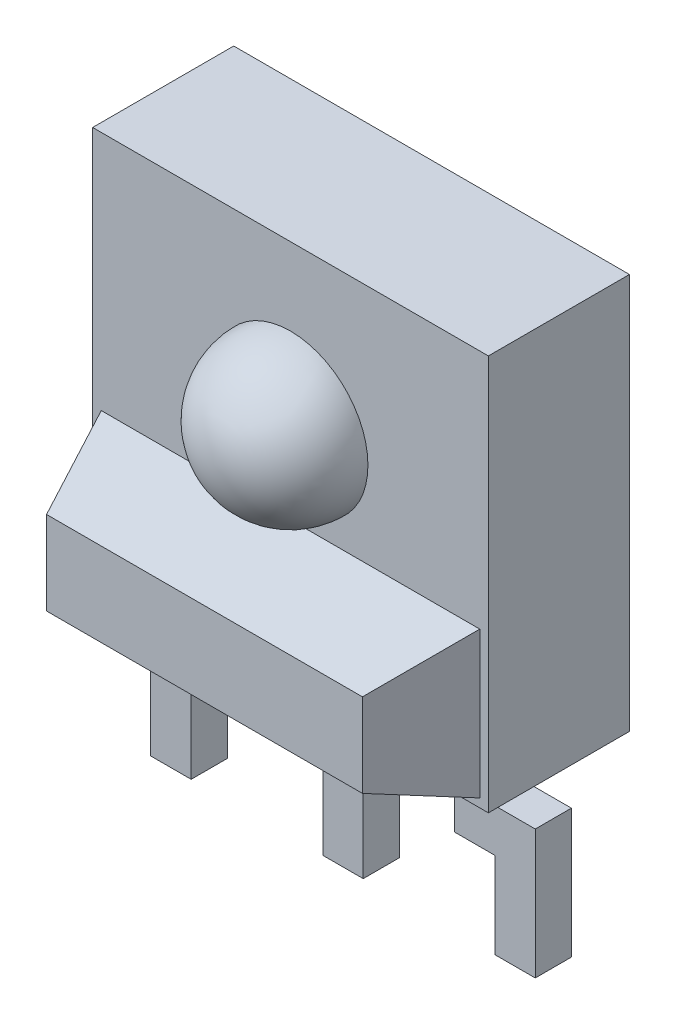
SolidWorks part; units mm, degrees
ref_plane "Front Plane" through (0, 0, 0) normal (0, 0, 1) x (1, 0, 0)
ref_plane "Top Plane" through (0, 0, 0) normal (0, 1, 0) x (1, 0, 0)
ref_plane "Right Plane" through (0, 0, 0) normal (1, 0, 0) x (0, 0, -1)
sketch "Sketch1" plane through (0, 0, 0) normal (0, 0, 1) x (1, 0, 0)
  line L0 (-1.295, 1) -> (-1.295, 0)
  line L1 (-0.235, 1) -> (0.235, 1)
  line L2 (-0.235, 1) -> (-0.235, -1)
  line L3 (-0.235, -1) -> (0.235, -1)
  line L4 (0.235, 1) -> (0.235, -1)
  line L5 (-0.235, 1) -> (0.235, -1) construction
  line L6 (-0.235, -1) -> (0.235, 1) construction
  line L7 (-1.295, 0) -> (-1.765, 0)
  line L8 (-1.765, 0) -> (-1.765, -1)
  line L9 (-1.765, -1) -> (-2.235, -1)
  line L10 (-2.235, -1) -> (-2.235, 0.5)
  line L11 (-2.235, 0.5) -> (-1.765, 0.5)
  line L12 (-1.765, 0.5) -> (-1.765, 1)
  line L13 (-1.765, 1) -> (-1.295, 1)
  line L14 (0, 1.2878) -> (0, -2.2675) construction
  line L15 (1.765, 1) -> (1.295, 1)
  line L16 (1.765, 0.5) -> (1.765, 1)
  line L17 (2.235, 0.5) -> (1.765, 0.5)
  line L18 (2.235, -1) -> (2.235, 0.5)
  line L19 (1.765, -1) -> (2.235, -1)
  line L20 (1.765, 0) -> (1.765, -1)
  line L21 (1.295, 0) -> (1.765, 0)
  line L22 (1.295, 1) -> (1.295, 0)
  point P0 (0, 0)
  point P13 (-2, -1)
  dimension "D1" = 0.47
  dimension "D2" = 2
  dimension "D3" = 0.47
  dimension "D4" = 0.47
  dimension "D5" = 1
  dimension "D6" = 1
  dimension "D7" = 0.5
  dimension "D8" = 2
  dimension "D9" = 0.47
extrude "Boss-Extrude1" add sketch "Sketch1" along normal mid plane 0.42
sketch "Sketch2" plane through (0, 1, 0) normal (0, 1, 0) x (1, 0, 0)
  line L1 (-2.3, 0.82) -> (2.3, 0.82)
  line L2 (-2.3, 0.82) -> (-2.3, -0.82)
  line L3 (-2.3, -0.82) -> (2.3, -0.82)
  line L4 (2.3, 0.82) -> (2.3, -0.82)
  line L5 (-2.3, 0.82) -> (2.3, -0.82) construction
  line L6 (-2.3, -0.82) -> (2.3, 0.82) construction
  point P0 (0, 0)
  dimension "D1" = 1.64
  dimension "D2" = 4.6
extrude "Boss-Extrude2" add sketch "Sketch2" along normal blind 4.6
sketch "Sketch3" plane through (0, 0, 0.82) normal (0, 0, 1) x (1, 0, 0)
  line L0 (-2.3, 5.6) -> (2.3, 5.6) construction
  line L1 (-2.3, 5.6) -> (-2.3, 1) construction
  line L2 (0, 4.7) -> (0, 2.9)
  arc A0 (0, 2.9) -> (0, 4.7) centre (0, 3.8) ccw
  dimension "D3" = 1.8
  dimension "D1" = 1.8
  dimension "D2" = 2.3
revolve "Revolve1" add sketch "Sketch3" angle 180 about L2
sketch "Sketch4" plane through (0, 0, 0.82) normal (0, 0, 1) x (1, 0, 0)
  line L0 (-2.3, 1) -> (2.3, 1) construction
  line L1 (-2.2, 2.8) -> (2.2, 2.8)
  line L2 (-2.2, 2.8) -> (-2.2, 1.1)
  line L3 (-2.2, 1.1) -> (2.2, 1.1)
  line L4 (2.2, 2.8) -> (2.2, 1.1)
  line L5 (-2.2, 2.8) -> (2.2, 1.1) construction
  line L6 (-2.2, 1.1) -> (2.2, 2.8) construction
  line L7 (2.3, 5.6) -> (2.3, 1) construction
  circle A0 centre (0, 3.8) radius 0.9 construction
  point P0 (0, 1.95)
  dimension "D1" = 0.1
  dimension "D2" = 1
  dimension "D3" = 0.1
extrude "Boss-Extrude3" add sketch "Sketch4" along normal blind 1
chamfer "Chamfer1" distance 1 angle 20 4 edges at (0, 1.1, 1.82) (-2.2, 1.95, 1.82) (2.2, 1.95, 1.82) (0, 2.8, 1.82) first distance on face at (0, 1.1, 1.32) first distance on face at (-2.2, 1.95, 1.32) first distance on face at (2.2, 1.95, 1.32) first distance on face at (0, 2.8, 1.32)
